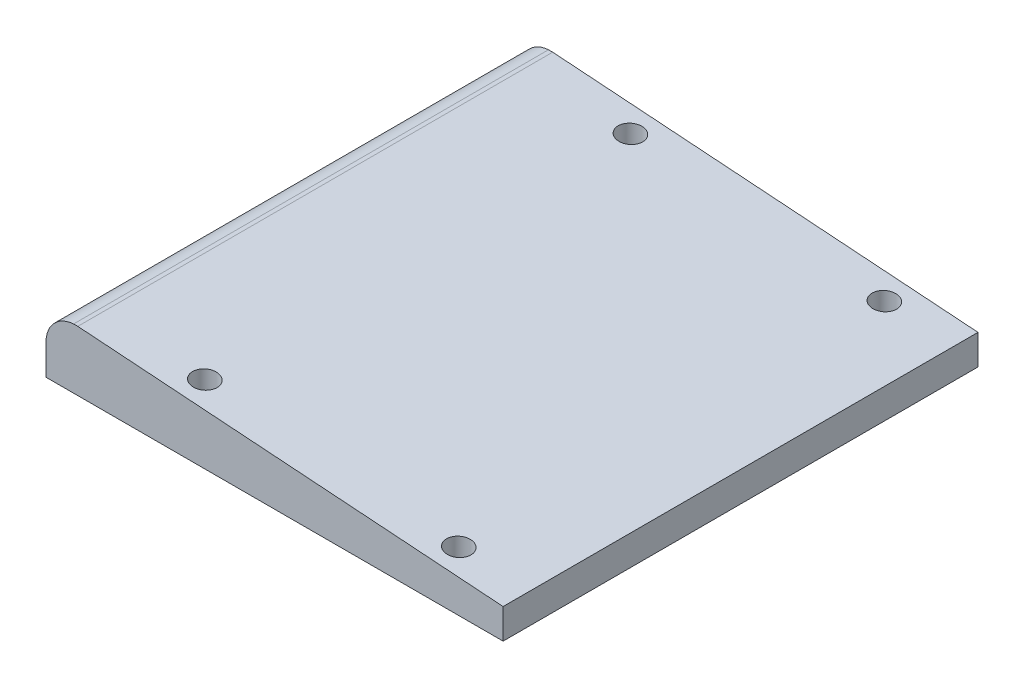
SolidWorks part; units mm, degrees
ref_plane "Front Plane" through (0, 0, 0) normal (0, 0, 1) x (1, 0, 0)
ref_plane "Top Plane" through (0, 0, 0) normal (0, 1, 0) x (1, 0, 0)
ref_plane "Right Plane" through (0, 0, 0) normal (1, 0, 0) x (0, 0, -1)
sketch "Sketch1" plane through (0, 0, 0) normal (0, 1, 0) x (1, 0, 0)
  line L0 (-95.8276, 0) -> (95.8276, 0) construction
  line L1 (-114.3, -118.75) -> (114.3, -118.75)
  line L2 (-114.3, -118.75) -> (-114.3, 118.75)
  line L3 (-114.3, 118.75) -> (114.3, 118.75)
  line L4 (114.3, -118.75) -> (114.3, 118.75)
  line L5 (-114.3, -118.75) -> (114.3, 118.75) construction
  line L6 (-114.3, 118.75) -> (114.3, -118.75) construction
  point P0 (0, 0)
  point P6 (79.8, 106.42)
  point P7 (-47.2, 106.42)
  point P8 (0, 0)
  point P9 (0, 0)
  point P10 (0, 0)
  point P13 (79.8, -106.42)
  point P14 (-47.2, -106.42)
  dimension "D1" = 228.6
  dimension "D2" = 237.5
  dimension "D3" = 12.33
  dimension "D4" = 34.5
  dimension "D5" = 161.5
extrude "Boss-Extrude1" add sketch "Sketch1" along normal blind 30
sketch "Sketch2" plane through (0, 0, 0) normal (0, 0, 1) x (1, 0, 0)
  line L0 (114.3, 15) -> (-98.3922, 30)
  line L1 (114.3, 30) -> (114.3, 0) construction
  line L2 (-114.3, 30) -> (114.3, 30) construction
  line L3 (-114.3, 30) -> (-114.3, 0) construction
  line L4 (-114.3, 30) -> (114.3, 30)
  line L5 (114.3, 30) -> (114.3, 15)
  arc A0 (-98.3922, 30) -> (-114.3, 15) centre (-99.4378, 15.1736) ccw
  arc A1 (-114.3, 15) -> (-114.3, 30) centre (527.7654, 22.5) cw
extrude "Cut-Extrude1" cut sketch "Sketch2" against normal through all both and the other way through all contours L5 L4 L0 | A1 A0 L4 | A0 A1 L4 L5 L0 region at (-111.0524, 26.6428, 0) region at (43.4026, 25, 0)
ref_plane "Plane1" through (0, 30.0368, 0) normal (0, 1, 0) x (1, 0, 0)
hole_wizard "CBORE for M5 Hex Head Bolt1" positions "Sketch8" profile "Sketch6" counterbore size "M5" standard "ANSI Metric" end condition through all
sketch "Sketch8" plane through (0, 30.0368, 0) normal (0, 1, 0) x (1, 0, 0)
  point P0 (-47.2, 106.42)
  point P3 (79.8, 106.42)
  point P6 (79.8, -106.42)
  point P9 (-47.2, -106.42)
sketch "Sketch6" plane through (-47.2, 30.0368, -106.42) normal (1, 0, 0) x (0, 0, 1)
  line L0 (0, 0) -> (0, 30.0368)
  line L1 (0, 30.0368) -> (2.75, 30.0368)
  line L3 (2.75, 30.0368) -> (2.75, 23.58)
  line L4 (2.75, 23.58) -> (6.12, 23.58)
  line L5 (6.12, 23.58) -> (6.12, 0)
  line L7 (6.12, 0) -> (0, 0)
  line L11 (0, -6.35) -> (0, 107.95) construction
  dimension "Thru Hole Dia." = 5.5
  dimension "Thru Hole Depth" = 30.0368
  dimension "C'Bore Dia." = 12.24
  dimension "C'Bore Depth" = 23.58
